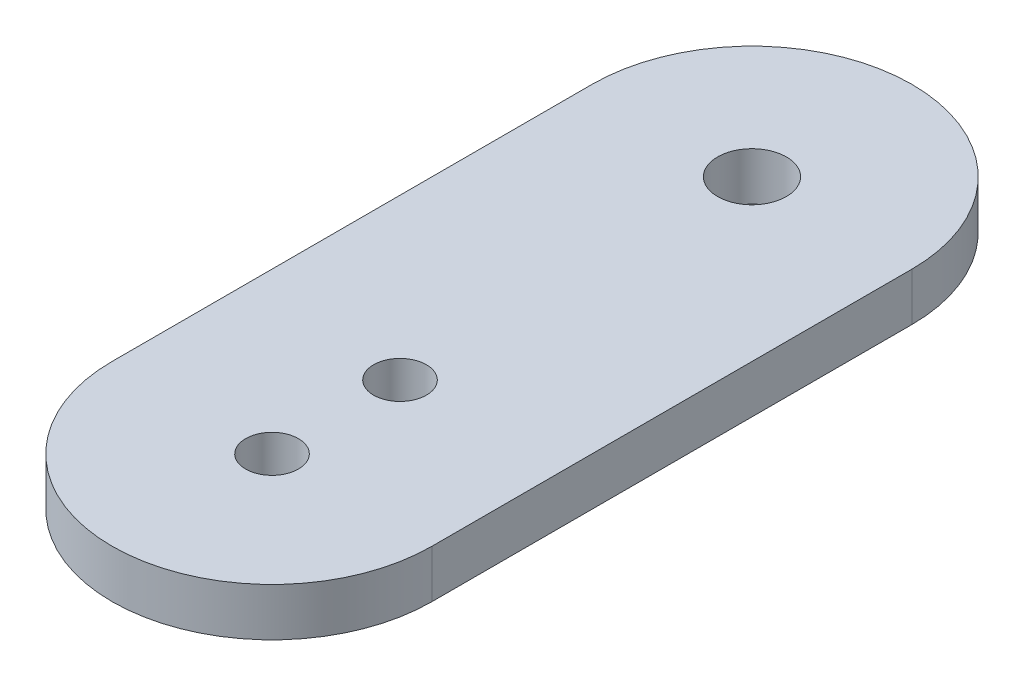
SolidWorks part; units mm, degrees
ref_plane "Front Plane" through (0, 0, 0) normal (0, 0, 1) x (1, 0, 0)
ref_plane "Top Plane" through (0, 0, 0) normal (0, 1, 0) x (1, 0, 0)
ref_plane "Right Plane" through (0, 0, 0) normal (1, 0, 0) x (0, 0, -1)
sketch "Sketch2" plane through (0, 0, 0) normal (0, 1, 0) x (1, 0, 0)
  line L0 (0, 0) -> (0, 30) construction
  line L1 (-10, 0) -> (-10, 30)
  line L2 (10, 0) -> (10, 30)
  arc A0 (-10, 0) -> (10, 0) centre (0, 0) ccw
  arc A1 (10, 30) -> (-10, 30) centre (0, 30) ccw
  point P3 (0, 15)
  dimension "D2" = 10
  dimension "D1" = 30
extrude "Boss-Extrude1" add sketch "Sketch2" along normal blind 3
sketch "Sketch3" plane through (0, 3, 0) normal (0, 1, 0) x (1, 0, 0)
  circle A0 centre (0, 0) radius 1.65
  circle A1 centre (0, 8) radius 1.65
  circle A2 centre (0, 30) radius 2.15
  dimension "D1" = 3.3
  dimension "D2" = 3.3
  dimension "D4" = 4.3
  dimension "D3" = 8
extrude "Cut-Extrude1" cut sketch "Sketch3" against normal blind 3
